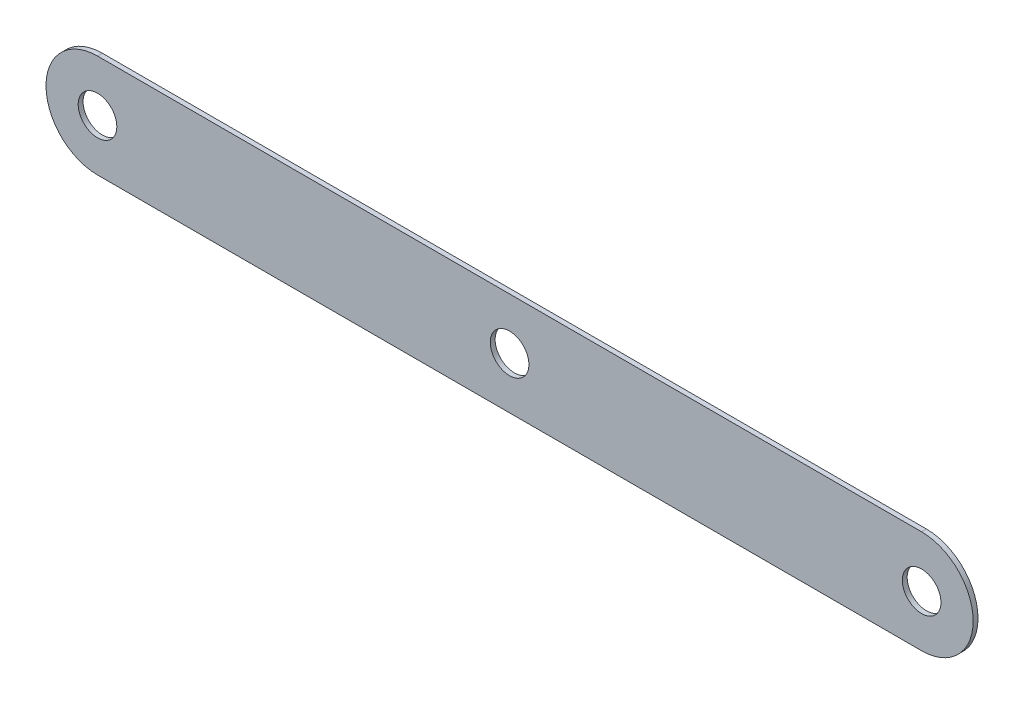
SolidWorks part; units mm, degrees
material "Alloy Steel"
ref_plane "Front" through (0, 0, 0) normal (0, 0, 1) x (1, 0, 0)
ref_plane "Top" through (0, 0, 0) normal (0, 1, 0) x (1, 0, 0)
ref_plane "Right" through (0, 0, 0) normal (1, 0, 0) x (0, 0, -1)
sketch "Sketch1" plane through (0, 0, 0) normal (0, 0, 1) x (1, 0, 0)
  line L1 (-101.6, 12.7) -> (101.6, 12.7)
  line L2 (-101.6, 12.7) -> (-101.6, -12.7)
  line L3 (-101.6, -12.7) -> (101.6, -12.7)
  line L4 (101.6, 12.7) -> (101.6, -12.7)
  line L5 (-101.6, 12.7) -> (101.6, -12.7) construction
  line L6 (-101.6, -12.7) -> (101.6, 12.7) construction
  arc A0 (-101.6, 12.7) -> (-101.6, -12.7) centre (-101.6, 0) ccw
  arc A1 (101.6, 12.7) -> (101.6, -12.7) centre (101.6, 0) cw
  point P0 (0, 0)
  dimension "D3" = 12.7
  dimension "D1" = 203.2
  dimension "D2" = 25.4
extrude "Boss-Extrude1" add sketch "Sketch1" along normal blind 1.2 contours L4 L1 L2 L3 | A1 L4 | L2 A0 region at (0, 0, 0) region at (-106.99, 0, 0) region at (106.99, 0, 0)
sketch "Sketch2" plane through (0, 0, 1.2) normal (0, 0, 1) x (1, 0, 0)
  circle A0 centre (0, 0) radius 4.7625
  dimension "D1" = 9.525
extrude "Cut-Extrude1" cut sketch "Sketch2" against normal through all
sketch "Sketch3" plane through (0, 0, 1.2) normal (0, 0, 1) x (1, 0, 0)
  circle A0 centre (-101.6, 0) radius 4.7625
  circle A1 centre (101.6, 0) radius 4.7625
  dimension "D1" = 9.525
  dimension "D2" = 9.525
extrude "Cut-Extrude2" cut sketch "Sketch3" against normal through all
